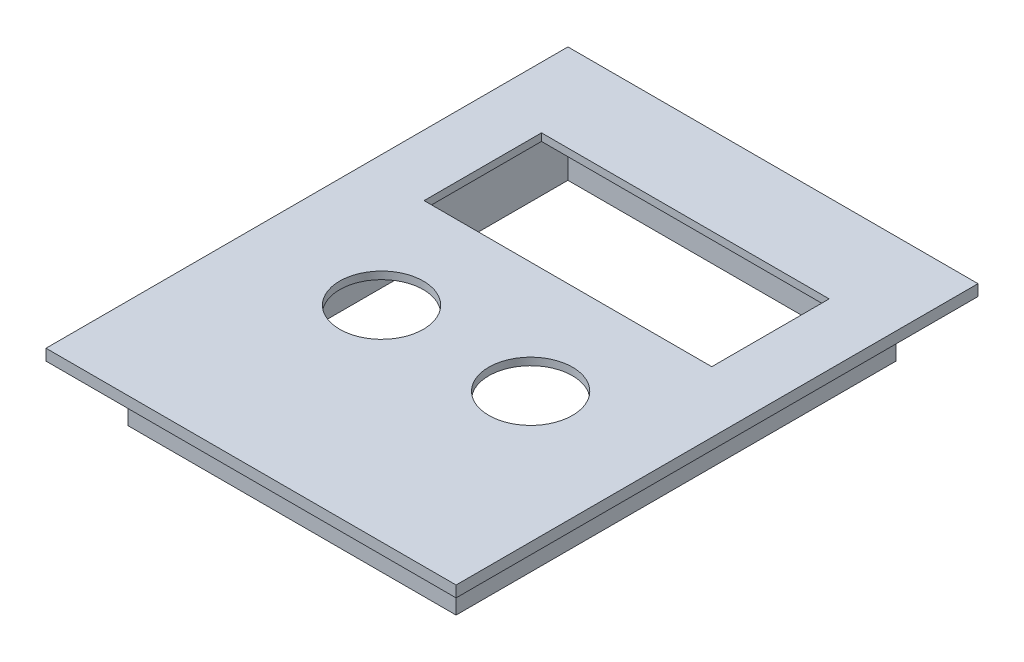
SolidWorks part; units mm, degrees
material "PLA"
ref_plane "Front Plane" through (0, 0, 0) normal (0, 0, 1) x (1, 0, 0)
ref_plane "Top Plane" through (0, 0, 0) normal (0, 1, 0) x (1, 0, 0)
ref_plane "Right Plane" through (0, 0, 0) normal (1, 0, 0) x (0, 0, -1)
sketch "Sketch1" plane through (0, 0, 0) normal (0, 1, 0) x (1, 0, 0)
  line L1 (69.85, -88.9) -> (-69.85, -88.9)
  line L2 (69.85, -88.9) -> (69.85, 88.9)
  line L3 (69.85, 88.9) -> (-69.85, 88.9)
  line L4 (-69.85, -88.9) -> (-69.85, 88.9)
  line L5 (69.85, -88.9) -> (-69.85, 88.9) construction
  line L6 (69.85, 88.9) -> (-69.85, -88.9) construction
  point P0 (0, 0)
  dimension "D1" = 139.7
  dimension "D2" = 177.8
extrude "Boss-Extrude1" add sketch "Sketch1" along normal blind 3.81
sketch "Sketch2" plane through (0, 0, 0) normal (0, -1, 0) x (1, 0, 0)
  line L1 (-55.88, -74.93) -> (55.88, -74.93)
  line L2 (-55.88, -74.93) -> (-55.88, 74.93)
  line L3 (-55.88, 74.93) -> (55.88, 74.93)
  line L4 (55.88, -74.93) -> (55.88, 74.93)
  line L5 (-55.88, -74.93) -> (55.88, 74.93) construction
  line L6 (-55.88, 74.93) -> (55.88, -74.93) construction
  point P0 (0, 0)
  dimension "D1" = 149.86
  dimension "D2" = 111.76
extrude "Boss-Extrude2" add sketch "Sketch2" along normal blind 19.05
shell "Shell1" thickness 2.54 removed face at (0, -19.05, 0)
sketch "Sketch3" plane through (0, 3.81, 0) normal (0, 1, 0) x (1, 0, 0)
  line L0 (69.85, 88.9) -> (-69.85, 88.9) construction
  line L1 (49, 19.05) -> (-49, 19.05)
  line L2 (49, 19.05) -> (49, 59.05)
  line L3 (49, 59.05) -> (-49, 59.05)
  line L4 (-49, 19.05) -> (-49, 59.05)
  line L5 (49, 19.05) -> (-49, 59.05) construction
  line L6 (49, 59.05) -> (-49, 19.05) construction
  line L7 (0, 0) -> (0, 88.9) construction
  circle A0 centre (-25.4, -19.05) radius 14.25
  circle A1 centre (25.4, -19.05) radius 14.25
  point P0 (0, 39.05)
  dimension "D6" = 38.1
  dimension "D5" = 38.1
  dimension "D7" = 28.5
  dimension "D1" = 40
  dimension "D2" = 98
  dimension "D3" = 19.05
  dimension "D4" = 50.8
  dimension "D8" = 25.4
extrude "Cut-Extrude1" cut sketch "Sketch3" against normal through all
sketch "Sketch4" plane through (0, 1.27, 0) normal (0, -1, 0) x (1, 0, 0)
  line L0 (-49, -39.05) -> (49, -39.05) construction
  line L1 (-49, -59.05) -> (-49, -19.05) construction
  line L2 (49, -19.05) -> (49, -59.05) construction
  line L3 (0, -19.05) -> (0, -59.05) construction
  line L4 (-49, -19.05) -> (49, -19.05) construction
  line L5 (49, -59.05) -> (-49, -59.05) construction
  line L7 (46.5, -66.55) -> (-46.5, -66.55) construction
  line L8 (46.5, -66.55) -> (46.5, -11.55) construction
  line L9 (46.5, -11.55) -> (-46.5, -11.55) construction
  line L10 (-46.5, -66.55) -> (-46.5, -11.55) construction
  line L11 (46.5, -66.55) -> (-46.5, -11.55) construction
  line L12 (46.5, -11.55) -> (-46.5, -66.55) construction
  circle A0 centre (-46.5, -11.55) radius 1.25
  circle A1 centre (-46.5, -11.55) radius 3
  circle A2 centre (46.5, -11.55) radius 3
  circle A3 centre (46.5, -11.55) radius 1.25
  circle A4 centre (46.5, -66.55) radius 3
  circle A5 centre (46.5, -66.55) radius 1.25
  circle A6 centre (-46.5, -66.55) radius 3
  circle A7 centre (-46.5, -66.55) radius 1.25
  point P12 (0, -39.05)
  dimension "D3" = 6
  dimension "D4" = 2.5
  dimension "D1" = 93
  dimension "D2" = 55
extrude "Boss-Extrude3" add sketch "Sketch4" along normal blind 2.54
